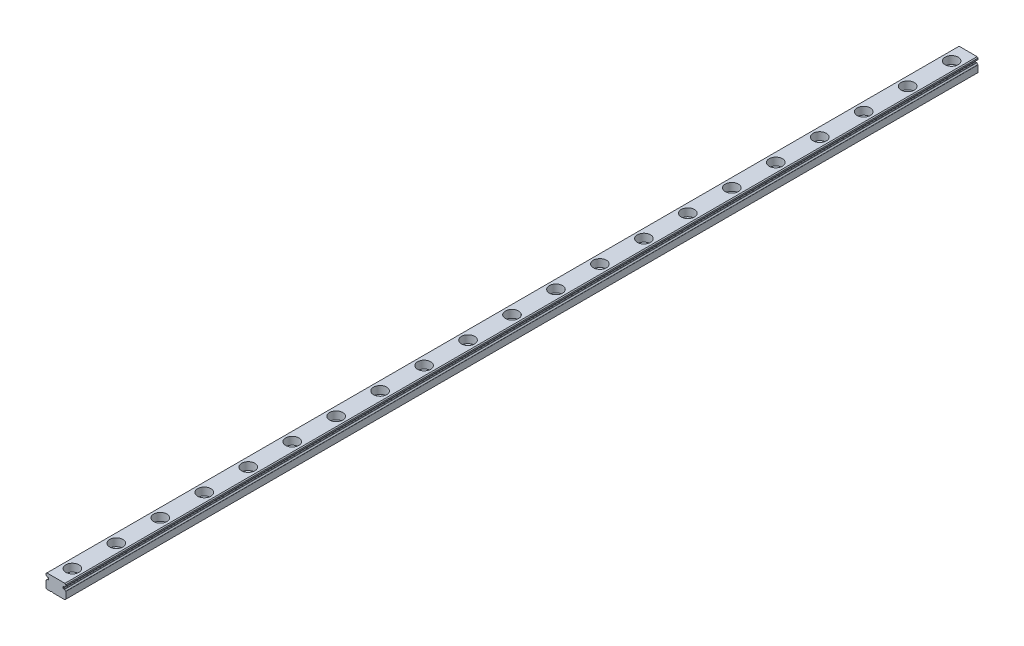
SolidWorks part; units mm, degrees
ref_plane "Front Plane" through (0, 0, 0) normal (0, 0, 1) x (1, 0, 0)
ref_plane "Top Plane" through (0, 0, 0) normal (0, 1, 0) x (1, 0, 0)
ref_plane "Right Plane" through (0, 0, 0) normal (1, 0, 0) x (0, 0, -1)
sketch "Sketch1" plane through (0, 0, 0) normal (0, 0, 1) x (1, 0, 0)
  point P0 (0, 0)
  line B0 (-1.4, -6.5) -> (4.1, -6.5)
  line B1 (4.1, -6.5) -> (4.5, -6.1)
  line B2 (4.5, -6.1) -> (4.5, -3.0583)
  line B3 (3.8235, -2.4365) -> (3.4826, -2.4066)
  line B4 (3.3, -2.2074) -> (3.3, -1.7926)
  line B5 (3.4826, -1.5934) -> (3.8235, -1.5635)
  line B6 (4.5, -0.9417) -> (4.5, -0.4)
  line B7 (4.5, -0.4) -> (4.1, 0)
  line B8 (4.1, 0) -> (-4.1, 0)
  line B9 (-4.1, 0) -> (-4.5, -0.4)
  line B10 (-4.5, -0.4) -> (-4.5, -0.9417)
  line B11 (-3.8235, -1.5635) -> (-3.4826, -1.5934)
  line B12 (-3.3, -1.7926) -> (-3.3, -2.2074)
  line B13 (-3.4826, -2.4066) -> (-3.8235, -2.4365)
  line B14 (-4.5, -3.0583) -> (-4.5, -6.1)
  line B15 (-4.5, -6.1) -> (-4.1, -6.5)
  line B16 (-4.1, -6.5) -> (-2.2, -6.5)
  arc B17 (4.5, -3.0583) -> (4.4087, -2.9203) centre (4.35, -3.0583) ccw
  arc B18 (3.9395, -2.5095) -> (4.4087, -2.9203) centre (4.8, -2) ccw
  arc B19 (3.9395, -2.5095) -> (3.8235, -2.4365) centre (3.8104, -2.5859) ccw
  arc B20 (3.3, -2.2074) -> (3.4826, -2.4066) centre (3.5, -2.2074) ccw
  arc B21 (3.4826, -1.5934) -> (3.3, -1.7926) centre (3.5, -1.7926) ccw
  arc B22 (3.8235, -1.5635) -> (3.9395, -1.4905) centre (3.8104, -1.4141) ccw
  arc B23 (4.4087, -1.0797) -> (3.9395, -1.4905) centre (4.8, -2) ccw
  arc B24 (4.4087, -1.0797) -> (4.5, -0.9417) centre (4.35, -0.9417) ccw
  arc B25 (-4.5, -0.9417) -> (-4.4087, -1.0797) centre (-4.35, -0.9417) ccw
  arc B26 (-3.9395, -1.4905) -> (-4.4087, -1.0797) centre (-4.8, -2) ccw
  arc B27 (-3.9395, -1.4905) -> (-3.8235, -1.5635) centre (-3.8104, -1.4141) ccw
  arc B28 (-3.3, -1.7926) -> (-3.4826, -1.5934) centre (-3.5, -1.7926) ccw
  arc B29 (-3.4826, -2.4066) -> (-3.3, -2.2074) centre (-3.5, -2.2074) ccw
  arc B30 (-3.8235, -2.4365) -> (-3.9395, -2.5095) centre (-3.8104, -2.5859) ccw
  arc B31 (-4.4087, -2.9203) -> (-3.9395, -2.5095) centre (-4.8, -2) ccw
  arc B32 (-4.4087, -2.9203) -> (-4.5, -3.0583) centre (-4.35, -3.0583) ccw
  arc B33 (-1.4, -6.5) -> (-2.2, -6.5) centre (-1.8, -6.8) ccw
sketch_block_instance "Block1-1"
sketch_block "Block1"
extrude "Boss-Extrude1" add sketch "Sketch1" along normal mid plane 415
sketch "Sketch2" plane through (0, 0, 0) normal (0, 1, 0) x (1, 0, 0)
  line L0 (0, -207.5) -> (0, 207.5) construction
  line L1 (4.1, -207.5) -> (-4.1, -207.5) construction
  line L2 (4.1, 207.5) -> (-4.1, 207.5) construction
  point P6 (0, -200)
  point P9 (0, -180)
  point P10 (0, -160)
  point P11 (0, -140)
  point P12 (0, -120)
  point P13 (0, -100)
  point P14 (0, -80)
  point P15 (0, -60)
  point P16 (0, -40)
  point P17 (0, -20)
  point P18 (0, 0)
  point P19 (0, 20)
  point P20 (0, 40)
  point P21 (0, 60)
  point P22 (0, 80)
  point P23 (0, 100)
  point P24 (0, 120)
  point P25 (0, 140)
  point P26 (0, 160)
  point P27 (0, 180)
  point P28 (0, 200)
  point P29 (0, 220)
  point P30 (0, 240)
  point P31 (0, 260)
  point P32 (0, 280)
  point P33 (0, 300)
  point P34 (0, 320)
  point P35 (0, 340)
  point P36 (0, 360)
  point P37 (0, 380)
  dimension "D1" = 30
  dimension "D2" = 20
  dimension "D3" = 7.5
sketch "Sketch3" plane through (0, 0, 0) normal (0, 1, 0) x (1, 0, 0)
  circle A0 centre (0, -200) radius 3
  circle A1 centre (0, -200) radius 1.75
  dimension "D1" = 3.5
  dimension "D2" = 6
extrude "Cut-Extrude2" cut sketch "Sketch3" against normal through all contours A1
extrude "Cut-Extrude3" cut sketch "Sketch3<3>" against normal blind 3.5
sketch "Sketch3<3>" plane through (0, 0, 0) normal (0, 1, 0) x (1, 0, 0) same geometry as "Sketch3"
pattern_sketch "Sketch-Pattern1" of "Cut-Extrude2", "Cut-Extrude3" driven by "Sketch2"
ref_plane "Groove Centerline" through (0, -2, 0) normal (0, -1, 0) x (-1, 0, 0)
